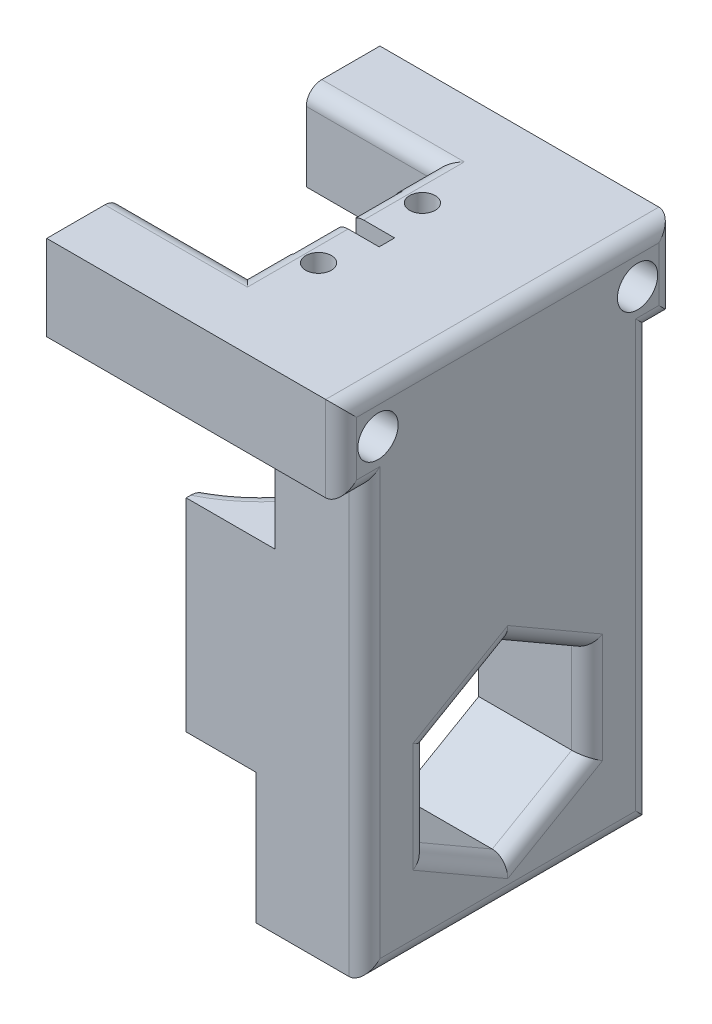
SolidWorks part; units mm, degrees
material "ABS"
ref_plane "Front Plane" through (0, 0, 0) normal (0, 0, 1) x (1, 0, 0)
ref_plane "Top Plane" through (0, 0, 0) normal (0, 1, 0) x (1, 0, 0)
ref_plane "Right Plane" through (0, 0, 0) normal (1, 0, 0) x (0, 0, -1)
sketch "Sketch2" plane through (0, 0, 0) normal (1, 0, 0) x (0, 0, -1)
  line L1 (0, 15.0313) -> (-13.0175, 7.5157)
  line L2 (-13.0175, 7.5157) -> (-13.0175, -7.5157)
  line L3 (-13.0175, -7.5157) -> (0, -15.0313)
  line L4 (0, -15.0313) -> (13.0175, -7.5157)
  line L5 (13.0175, -7.5157) -> (13.0175, 7.5157)
  line L6 (13.0175, 7.5157) -> (0, 15.0313)
  line L7 (-23.495, -21.3813) -> (23.495, -21.3813)
  line L8 (-23.495, -21.3813) -> (-23.495, 48.4687)
  line L9 (-23.495, 62.4387) -> (23.495, 62.4387)
  line L10 (23.495, -21.3813) -> (23.495, 48.4687)
  line L11 (-23.495, 62.4387) -> (-27.305, 62.4387)
  line L13 (-23.495, 48.4687) -> (-27.305, 48.4687)
  line L14 (-27.305, 62.4387) -> (-27.305, 48.4687)
  line L15 (23.495, 62.4387) -> (27.305, 62.4387)
  line L17 (23.495, 48.4687) -> (27.305, 48.4687)
  line L18 (27.305, 62.4387) -> (27.305, 48.4687)
  circle A0 centre (0, 0) radius 13.0175 construction
  point P13 (0, -21.3813)
  point P20 (-25.4, 48.4687)
  dimension "D1" = 26.035
  dimension "D2" = 6.35
  dimension "D3" = 46.99
  dimension "D4" = 83.82
  dimension "D5" = 3.81
  dimension "D7" = 13.97
extrude "Boss-Extrude1" add sketch "Sketch2" along normal blind 17.78
sketch "Sketch4" plane through (0, 0, 0) normal (-1, 0, 0) x (0, 0, 1)
  line L0 (-23.495, -21.3813) -> (-23.495, 48.4687) construction
  line L1 (-23.495, 16.3013) -> (23.495, 16.3013)
  line L2 (-23.495, 16.3013) -> (-23.495, 48.4687)
  line L3 (-23.495, 62.4387) -> (23.495, 62.4387)
  line L4 (23.495, 16.3013) -> (23.495, 48.4687)
  line L5 (23.495, 48.4687) -> (23.495, -21.3813) construction
  line L6 (-27.305, 62.4387) -> (27.305, 62.4387) construction
  line L7 (27.305, 62.4387) -> (27.305, 48.4687) construction
  line L8 (27.305, 48.4687) -> (23.495, 48.4687) construction
  line L9 (-23.495, 48.4687) -> (-27.305, 48.4687) construction
  line L10 (-27.305, 48.4687) -> (-27.305, 62.4387) construction
  line L11 (27.305, 62.4387) -> (27.305, 48.4687)
  line L12 (27.305, 48.4687) -> (23.495, 48.4687)
  line L13 (-23.495, 48.4687) -> (-27.305, 48.4687)
  line L14 (-27.305, 48.4687) -> (-27.305, 62.4387)
  line L15 (-27.305, 62.4387) -> (27.305, 62.4387)
  line M5 (23.495, -21.3813) -> (23.495, 48.4687)
  line M6 (27.305, 62.4387) -> (-27.305, 62.4387)
  line M7 (-23.495, 48.4687) -> (-23.495, -21.3813)
  line M15 (23.495, 48.4687) -> (27.305, 48.4687)
  line M16 (27.305, 48.4687) -> (27.305, 62.4387)
  line M17 (-27.305, 62.4387) -> (-27.305, 48.4687)
  line M18 (-27.305, 48.4687) -> (-23.495, 48.4687)
  dimension "D1" = 1.27
extrude "Boss-Extrude2" add sketch "Sketch4" along normal blind 11.43 contours L1 M7 M5 M15 M16 M6 M17 M18 region at (0, 40.1228, 0)
sketch "Sketch5" plane through (0, 62.4387, 0) normal (0, 1, 0) x (1, 0, 0)
  line L0 (0, 0) -> (-22.7305, 0) construction
  line L2 (-11.43, -27.305) -> (-11.43, 27.305) construction
  circle A0 centre (-22.7305, 0) radius 34.925
  circle A1 centre (-22.7305, 0) radius 22.86
  dimension "D2" = 69.85
  dimension "D3" = 45.72
  dimension "D1" = 11.3005
extrude "Cut-Extrude1" cut sketch "Sketch5" against normal blind 15.24 from offset 13.97 contours A1 A0 | A1 region at (-56.6676, 62.4387, 0) region at (-22.7305, 62.4387, 0) offset against normal yes
extrude "Cut-Extrude2" cut sketch "Sketch5<3>" against normal blind 35.56 from surface contours A1 region at (-22.7305, 62.4387, 0) starting at face at (-1.8888, 33.2287, 0)
sketch "Sketch5<3>" plane through (0, 62.4387, 0) normal (0, 1, 0) x (1, 0, 0) same geometry as "Sketch5"
sketch "Sketch6" plane through (-11.43, 0, 0) normal (-1, 0, 0) x (0, 0, 1)
  line L12 (-27.305, 62.4387) -> (-27.305, 48.4687)
  line L13 (-27.305, 48.4687) -> (27.305, 48.4687)
  line L14 (27.305, 48.4687) -> (27.305, 62.4387)
  line L15 (27.305, 62.4387) -> (-27.305, 62.4387)
  line L16 (-27.305, 62.4387) -> (-27.305, 48.4687)
  line L17 (-27.305, 48.4687) -> (27.305, 48.4687)
  line L18 (27.305, 48.4687) -> (27.305, 62.4387)
  line L19 (27.305, 62.4387) -> (-27.305, 62.4387)
  dimension "D1" = 0
extrude "Boss-Extrude3" add sketch "Sketch6" along normal blind 19.05
sketch "Sketch7" plane through (0, 62.4387, 0) normal (0, 1, 0) x (1, 0, 0)
  line L0 (-30.48, -27.305) -> (-30.48, 27.305) construction
  line L1 (-30.48, 15.24) -> (-9.652, 15.24)
  line L2 (-30.48, 15.24) -> (-30.48, -15.24)
  line L3 (-30.48, -15.24) -> (-9.652, -15.24)
  line L4 (-9.652, 15.24) -> (-9.652, -15.24)
  line L6 (-9.652, -8.89) -> (-8.382, -8.89)
  line L7 (-9.652, -8.89) -> (-9.652, 8.89)
  line L8 (-9.652, 8.89) -> (-8.382, 8.89)
  line L9 (-8.382, -8.89) -> (-8.382, 8.89)
  point P6 (-9.652, 0)
  point P12 (-8.382, 0)
  line M6 (-30.48, 27.305) -> (-30.48, -27.305)
  dimension "D1" = 30.48
  dimension "D2" = 20.828
  dimension "D3" = 17.78
  dimension "D4" = 1.27
extrude "Cut-Extrude3" cut sketch "Sketch7" against normal up to surface (13.97 mm away) contours L6 L9 L8 L4 | L4 L1 L3 M6 region at (-20.066, 62.4387, 0) region at (-9.017, 62.4387, 0) up to face at (3.1831, 48.4687, 0)
sketch "Sketch8" plane through (0, 62.4387, 0) normal (0, 1, 0) x (1, 0, 0)
  line L0 (-9.652, -15.24) -> (-9.652, -8.89) construction
  line L1 (-9.652, -1.27) -> (-2.032, -1.27)
  line L2 (-9.652, -1.27) -> (-9.652, 1.27)
  line L3 (-9.652, 1.27) -> (-2.032, 1.27)
  line L4 (-2.032, -1.27) -> (-2.032, 1.27)
  point P6 (-5.842, -1.27)
  point P7 (-9.652, 0)
  dimension "D1" = 2.54
  dimension "D2" = 7.62
extrude "Cut-Extrude4" cut sketch "Sketch8" against normal blind 2.54
sketch "Sketch9" plane through (0, 62.4387, 0) normal (0, 1, 0) x (1, 0, 0)
  line L0 (17.78, 27.305) -> (17.78, -27.305) construction
  line L1 (17.78, -23.495) -> (-30.48, -23.495) construction
  line L2 (0, 0) -> (17.78, 0) construction
  circle A0 centre (-4.7193, -8.509) radius 1.27
  circle A1 centre (-4.7193, 8.509) radius 1.27
  point P0 (-4.7193, -8.509)
  point P9 (-4.7193, 8.509)
  dimension "D3" = 2.54
  dimension "D1" = 22.4993
  dimension "D2" = 14.986
hole_wizard "Tap Drill for M5x0.8 Tap1" positions "Sketch9" profile "Sketch10" hole size "M5x0.8" standard "ANSI Metric"
sketch "Sketch10" plane through (-4.7193, 62.4387, 8.509) normal (1, 0, 0) x (0, 0, 1)
  line L0 (0, 0) -> (0, 9.1358)
  line L1 (0, 9.1358) -> (2.1, 7.874)
  line L2 (2.1, 7.874) -> (2.1, 0)
  line L5 (2.1, 0) -> (0, 0)
  line L10 (0, 9.1358) -> (-2.1, 7.874) construction
  line L11 (0, -6.35) -> (0, 107.95) construction
  dimension "Hole Dia." = 4.2
  dimension "Hole Depth" = 7.874
  dimension "Drill Angle" = 118
sketch "Sketch11" plane through (0, 0, 0) normal (-1, 0, 0) x (0, 0, 1)
  line L0 (-15.494, 0) -> (-23.495, 0)
  line L1 (-23.495, -21.3813) -> (-23.495, 16.3013) construction
  line L2 (15.494, 0) -> (23.495, 0)
  line L3 (23.495, 16.3013) -> (23.495, -21.3813) construction
  line L4 (-23.495, 16.3013) -> (-2.4302, 16.3013) construction
  line L5 (-23.495, 16.3013) -> (23.495, 16.3013)
  line L6 (-23.495, 16.3013) -> (-23.495, 0)
  line L7 (23.495, 16.3013) -> (23.495, 0)
  arc A0 (-15.494, 0) -> (15.494, 0) centre (0, 0) cw
  line M1 (23.495, 16.3013) -> (2.4302, 16.3013)
  line M2 (-23.495, 16.3013) -> (-23.495, -21.3813)
  line M4 (23.495, -21.3813) -> (23.495, 16.3013)
  line M33 (-2.4302, 13.6282) -> (-2.4302, 16.3013)
  line M34 (-2.4302, 16.3013) -> (-23.495, 16.3013)
  line M35 (2.4302, 16.3013) -> (2.4302, 13.6282)
  dimension "D1" = 15.494
extrude "Boss-Extrude4" add sketch "Sketch11" along normal up to surface (11.43 mm away) contours L0 A0 L2 M4 M1 M2 | L0 A0 M33 M34 M2 | A0 L5 M33 M35 region at (0, 9.6095, -16.9326) region at (0, 15.8639, 0) region at (0, 9.6095, 16.9326) up to face at (-11.43, 24.765, 21.6833)
sketch "Sketch12" plane through (-30.48, 0, 0) normal (-1, 0, 0) x (0, 0, 1)
  line L1 (-21.2725, 55.4537) -> (-21.2725, 48.4687) construction
  line L3 (-27.305, 55.4537) -> (-21.2725, 55.4537) construction
  line L5 (-21.2725, 55.4537) -> (-21.2725, 62.4387) construction
  line L7 (-21.2725, 55.4537) -> (-15.24, 55.4537) construction
  line L8 (-15.24, 48.4687) -> (-15.24, 62.4387) construction
  line L9 (0, 0) -> (0, 62.4387) construction
  line L10 (1.27, 62.4387) -> (-1.27, 62.4387) construction
  line L11 (-15.24, 62.4387) -> (-27.305, 62.4387) construction
  line L12 (-23.495, 48.4687) -> (23.495, 48.4687) construction
  line L13 (-27.305, 62.4387) -> (-27.305, 48.4687) construction
  circle A0 centre (-21.2725, 55.4537) radius 3.302
  circle A1 centre (21.2725, 55.4537) radius 3.302
  dimension "D1" = 6.604
extrude "Cut-Extrude5" cut sketch "Sketch12" against normal through all
fillet "Fillet1" radius 2.54 1 edges at (0.1295, 33.2287, 0)
fillet "Fillet3" radius 2.54 18 edges at (17.78, 11.2735, 6.5087) (17.78, 0, 13.0175) (17.78, -11.2735, 6.5087) (17.78, -11.2735, -6.5087) (17.78, 0, -13.0175) (17.78, 11.2735, -6.5087) (17.78, 62.4387, 0) (17.78, 13.5437, -23.495) (17.78, -21.3813, 0) (17.78, 13.5437, 23.495) (-20.066, 62.4387, 15.24) (-9.652, 62.4387, 12.065) (-9.652, 62.4387, -12.065) (-20.066, 62.4387, -15.24) (17.78, 48.4687, 25.4) (17.78, 55.4537, 27.305) (17.78, 55.4537, -27.305) (17.78, 48.4687, -25.4)
